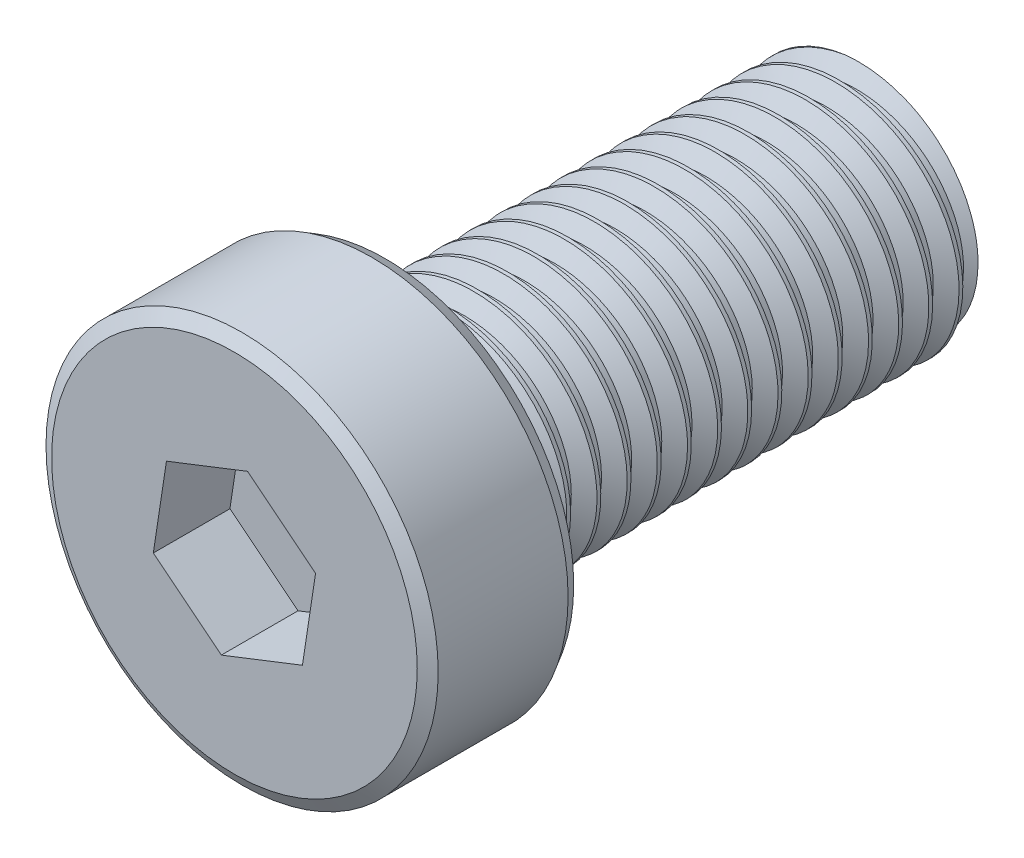
SolidWorks part; units mm, degrees
ref_plane "Front Plane" through (0, 0, 0) normal (0, 0, 1) x (1, 0, 0)
ref_plane "Top Plane" through (0, 0, 0) normal (0, 1, 0) x (1, 0, 0)
ref_plane "Right Plane" through (0, 0, 0) normal (1, 0, 0) x (0, 0, -1)
sketch "Sketch1" plane through (0, 0, 0) normal (0, 0, 1) x (1, 0, 0)
  circle A0 centre (0, 0) radius 6.5
  dimension "D1" = 13
extrude "Boss-Extrude1" add sketch "Sketch1" along normal blind 5
sketch "Sketch2" plane through (0, 0, 5) normal (0, 0, 1) x (1, 0, 0)
  line L1 (2.2547, -1.8027) -> (2.6885, 1.0512)
  line L2 (2.6885, 1.0512) -> (0.4339, 2.854)
  line L3 (0.4339, 2.854) -> (-2.2547, 1.8027)
  line L4 (-2.2547, 1.8027) -> (-2.6885, -1.0512)
  line L5 (-2.6885, -1.0512) -> (-0.4339, -2.854)
  line L6 (-0.4339, -2.854) -> (2.2547, -1.8027)
  circle A0 centre (0, 0) radius 2.5 construction
  dimension "D1" = 5
extrude "Cut-Extrude1" cut sketch "Sketch2" against normal blind 2.54
sketch "Sketch3" plane through (0, 0, 0) normal (0, 0, -1) x (-1, 0, 0)
  circle A0 centre (0, 0) radius 4
  dimension "D1" = 8
extrude "Boss-Extrude2" add sketch "Sketch3" along normal blind 16
chamfer "Chamfer1" distance 0.254 angle 60 3 edges at (-4, 0, -16) (6.5, 0, 5) (6.5, 0, 0)
thread "Thread1" pitch 1 start angle 0, offset 1.27, length 0, pitch 1, diameter 8
ref_plane "Plane1" through (4, 0, -17.016) normal (0, -1, 0) x (1, 0, 0)
sketch "Thread Profile1" plane through (4, 0, -17.016) normal (0, -1, 0) x (1, 0, 0)
  line L0 (0, 0) -> (0, 1) construction
  line L11 (0, 0) -> (0, 0.875)
  line L12 (0, 0.875) -> (-0.5413, 0.5625)
  line L13 (-0.5413, 0.5625) -> (-0.5413, 0.3125)
  line L15 (-0.5413, 0.3125) -> (0, 0)
  line L17 (-0.5413, 0.4375) -> (0, 0.4375) construction
  point P2 (0, 0)
  dimension "Pitch" = 1
  dimension "Profile_Angle" = 60
  dimension "Profile_Land" = 0.25
  dimension "Profile_Height" = 0.5413
